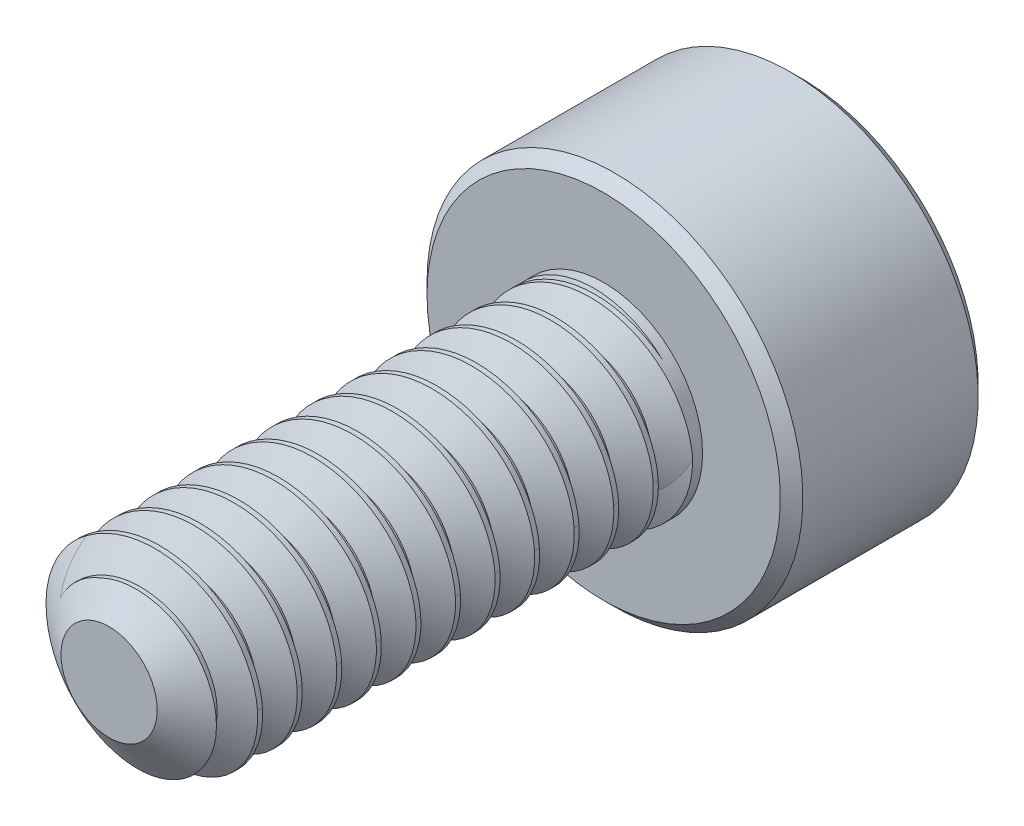
SolidWorks part; units mm, degrees
ref_plane "Front Plane" through (0, 0, 0) normal (0, 0, 1) x (1, 0, 0)
ref_plane "Top Plane" through (0, 0, 0) normal (0, 1, 0) x (1, 0, 0)
ref_plane "Right Plane" through (0, 0, 0) normal (1, 0, 0) x (0, 0, -1)
sketch "Sketch1" plane through (0, 0, 0) normal (0, 0, 1) x (1, 0, 0)
  circle A0 centre (0, 0) radius 1
  dimension "OD" = 2
extrude "Extrude1" add sketch "Sketch1" against normal blind 5
sketch "Sketch2" plane through (0, 0, 0) normal (0, 0, 1) x (1, 0, 0)
  circle A0 centre (0, 0) radius 1 construction
  circle A1 centre (0, 0) radius 1
curve "Helix/Spiral1" pitch 0.4 height 5.4 radius 1 centre (0, 0, 0) axis (0, 0, -1) start towards (0, 1, 0) parameters "pitch"=0.4
sketch "Sketch3" plane through (0, 0, 0) normal (1, 0, 0) x (0, 0, -1)
  line L0 (-0.35, 1) -> (-0.2, 0.7402)
  line L1 (-0.2, 0.7402) -> (-0.15, 0.7402)
  line L2 (-0.15, 0.7402) -> (0, 1)
  line L3 (-0.35, 1) -> (0, 1)
  line L4 (-0.175, 1) -> (-0.175, 0.7402) construction
  line L5 (-0.275, 0.8701) -> (-0.075, 0.8701) construction
  line L6 (0, 1) -> (0, -1) construction
  line L7 (0, -1) -> (5, -1) construction
  point P11 (1.8, -1)
  dimension "D1" = 0.05
  dimension "D2" = 0.2
  dimension "D3" = 60
  dimension "D4" = 1.8
sweep "Cut-Sweep1" cut profiles "Sketch3" path "Helix/Spiral1" align with end faces yes
sketch "Sketch4" plane through (0, 0, 0) normal (1, 0, 0) x (0, 0, -1)
  line L0 (0.3598, 1) -> (0, 0.4862)
  line L1 (0, 0.4862) -> (0, 1)
  line L2 (0.3598, 1) -> (0, 1)
  line L3 (-0.35, 1) -> (0, 1) construction
  line L4 (0, 0) -> (7.0209, 0) construction
  dimension "D1" = 55
  dimension "D2" = 0.254
revolve "Cut-Revolve1" cut sketch "Sketch4" angle 360 about L4
sketch "Sketch5" plane through (0, 0, 0) normal (1, 0, 0) x (0, 0, -1)
  line L0 (5, -0.7135) -> (5, 0.7473) construction
  line L1 (5, 1) -> (0.1203, 1)
  line L2 (5, 1) -> (5, 0)
  line L3 (5, 0) -> (0.0001, 0)
  line L4 (0.0001, 0.6698) -> (0.0001, 0)
  line L5 (0.1203, 1) -> (0.0001, 0.6698)
  line L6 (0, 0) -> (9.9695, 0) construction
  point P3 (0.0001, 1)
  point P10 (0.0001, 1)
  dimension "D1" = 0.3302
  dimension "Thread min" = 0.0001
  dimension "D3" = 20
revolve "partially thread" [suppressed] add sketch "Sketch5" angle 360 about L6
sketch "Sketch6" plane through (0, 0, -5) normal (0, 0, -1) x (-1, 0, 0)
  circle A0 centre (0, 0) radius 1.9
  dimension "head dia" = 3.8
extrude "Extrude2" add sketch "Sketch6" along normal blind 2
sketch "Sketch7" plane through (0, 0, -7) normal (0, 0, -1) x (-1, 0, 0)
  line L1 (0, 0.866) -> (-0.75, 0.433)
  line L2 (-0.75, 0.433) -> (-0.75, -0.433)
  line L3 (-0.75, -0.433) -> (0, -0.866)
  line L4 (0, -0.866) -> (0.75, -0.433)
  line L5 (0.75, -0.433) -> (0.75, 0.433)
  line L6 (0.75, 0.433) -> (0, 0.866)
  circle A0 centre (0, 0) radius 0.75 construction
  dimension "hex dia" = 1.5
extrude "Cut-Extrude1" cut sketch "Sketch7" against normal blind 1.125
sketch "Sketch8" plane through (0, 0, -7) normal (0, 0, -1) x (-1, 0, 0)
  circle A0 centre (0, 0) radius 0.866
extrude "Cut-Extrude2" cut sketch "Sketch8" against normal through all draft 45
chamfer "Chamfer1" distance 0.114 angle 45 2 edges at (-1.9, 0, -7) (-1.9, 0, -5)
sketch "Sketch9" plane through (0, 0, 0) normal (1, 0, 0) x (0, 0, -1)
  line L0 (0, 1) -> (0, -1) construction
  line L1 (2.2, 1) -> (2.2, -1) construction
  dimension "D1" = 2.2
sketch "Sketch10" plane through (0, 0, 0) normal (1, 0, 0) x (0, 0, -1)
  line L0 (5, 1) -> (5, 0)
  line L1 (5, 1) -> (4.9, 1)
  line L2 (4.9, 1) -> (4.4858, 0)
  line L3 (5, 0) -> (4.4858, 0)
  line L4 (5, 1.786) -> (5, -1.786) construction
  dimension "D1" = 22.5
  dimension "D2" = 0.1
revolve "Revolve1" add sketch "Sketch10" angle 360 about L3
equation "\"D3@Helix/Spiral1\" = \"screw length@Extrude1\"+\"pitch@Helix/Spiral1\""
equation "\"D1@Sketch3\" = \"pitch@Helix/Spiral1\"*.125"
equation "\"D2@Sketch3\" = \"pitch@Helix/Spiral1\"*.5"
equation "\"D1@Cut-Extrude1\" = \"hex dia@Sketch7\"*.75"
equation "\"D1@Chamfer1\" = \"head dia@Sketch6\"*.03"
equation "\"D1@Sketch9\" = \"pitch@Helix/Spiral1\"*5.5"
equation "\"D2@Sketch10\" = \"pitch@Helix/Spiral1\"*.25"
equation "\"D4@Sketch3\" = \"pitch@Helix/Spiral1\"*4.50"
